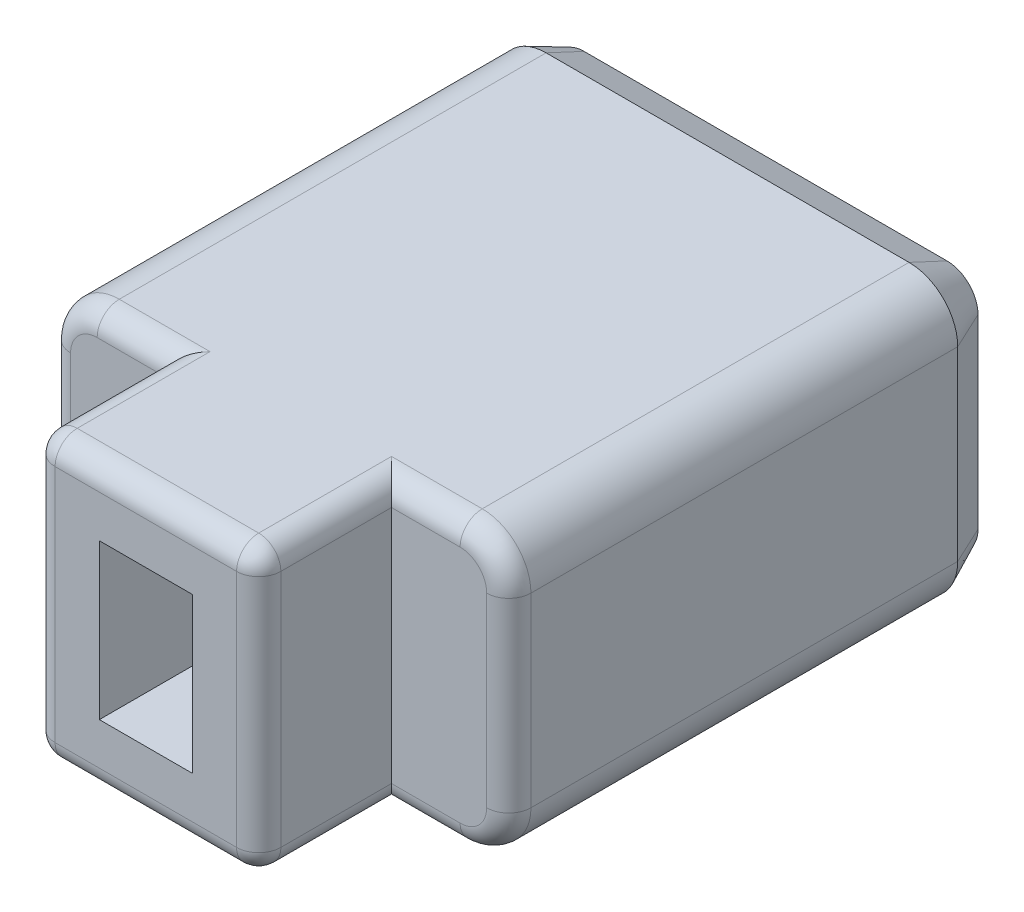
SolidWorks part; units mm, degrees
ref_plane "Plan de face" through (0, 0, 0) normal (0, 0, 1) x (1, 0, 0)
ref_plane "Plan de dessus" through (0, 0, 0) normal (0, 1, 0) x (1, 0, 0)
ref_plane "Plan de droite" through (0, 0, 0) normal (1, 0, 0) x (0, 0, -1)
sketch "Esquisse2" plane through (0, 0, 0) normal (0, 0, 1) x (1, 0, 0)
  line L1 (1.1, 0) -> (9.3, 0)
  line L2 (0, 1.1) -> (0, 5.3)
  line L3 (1.1, 6.4) -> (9.3, 6.4)
  line L4 (10.4, 1.1) -> (10.4, 5.3)
  arc A0 (9.3, 6.4) -> (10.4, 5.3) centre (9.3, 5.3) cw
  arc A1 (9.3, 0) -> (10.4, 1.1) centre (9.3, 1.1) ccw
  arc A2 (1.1, 0) -> (0, 1.1) centre (1.1, 1.1) cw
  arc A3 (0, 5.3) -> (1.1, 6.4) centre (1.1, 5.3) cw
  point P7 (10.4, 6.4)
  point P12 (0, 0)
  point P15 (0, 6.4)
  dimension "D3" = 1.1
  dimension "D1" = 10.4
  dimension "D2" = 6.4
extrude "Boss.-Extru.1" add sketch "Esquisse2" along normal blind 14
sketch "Esquisse3" plane through (0, 0, 14) normal (0, 0, 1) x (1, 0, 0)
  line L0 (0, 5.3) -> (0, 1.1) construction
  line L1 (4.15, 4.95) -> (6.25, 4.95)
  line L2 (4.15, 4.95) -> (4.15, 1.45)
  line L3 (4.15, 1.45) -> (6.25, 1.45)
  line L4 (6.25, 4.95) -> (6.25, 1.45)
  line L5 (10.4, 1.1) -> (10.4, 5.3) construction
  line L6 (9.3, 6.4) -> (1.1, 6.4) construction
  line L7 (1.1, 0) -> (9.3, 0) construction
  dimension "D1" = 2.1
  dimension "D2" = 3.5
  dimension "D3" = 4.15
  dimension "D4" = 4.15
  dimension "D5" = 1.45
  dimension "D6" = 1.45
extrude "Enlèv. mat.-Extru.1" cut sketch "Esquisse3" against normal blind 3
sketch "Esquisse4" plane through (0, 0, 14) normal (0, 0, 1) x (1, 0, 0)
  line L0 (2.65, 6.4) -> (2.65, 0)
  line L1 (9.3, 6.4) -> (1.1, 6.4) construction
  line L2 (1.1, 0) -> (9.3, 0) construction
  line L3 (2.65, 0) -> (7.75, 0)
  line L4 (7.75, 0) -> (7.75, 6.4)
  line L5 (7.75, 6.4) -> (2.65, 6.4)
  line L6 (4.15, 4.95) -> (4.15, 1.45) construction
  line L7 (6.25, 1.45) -> (6.25, 4.95) construction
  dimension "D1" = 1.5
  dimension "D2" = 1.5
extrude "Enlèv. mat.-Extru.2" cut sketch "Esquisse4" against normal blind 3 flip side to cut
fillet "Congé1" radius 0.5 18 edges at (8.525, 0, 11) (10.0778, 0.3222, 11) (10.4, 3.2, 11) (10.0778, 6.0778, 11) (1.875, 6.4, 11) (0.3222, 6.0778, 11) (1.875, 0, 11) (0.3222, 0.3222, 11) (7.75, 6.4, 12.5) (2.65, 6.4, 12.5) (7.75, 0, 12.5) (2.65, 0, 12.5) (2.65, 3.2, 14) (5.2, 6.4, 14) (7.75, 3.2, 14) (5.2, 0, 14) (8.525, 6.4, 11) (0, 3.2, 11)
chamfer "Chanfrein1" distance 0.4 angle 65 8 edges at (5.2, 0, 0) (10.0778, 0.3222, 0) (0.3222, 0.3222, 0) (10.4, 3.2, 0) (0, 3.2, 0) (10.0778, 6.0778, 0) (0.3222, 6.0778, 0) (5.2, 6.4, 0) first distance on face at (5.2, 3.2, 0)
sketch "Esquisse5" plane through (0, 0, 0) normal (0, 0, -1) x (-1, 0, 0)
  line L0 (-0.4, 5.3) -> (-10, 5.3) construction
  arc A0 (-9.3, 6) -> (-10, 5.3) centre (-9.3, 5.3) ccw construction
  text T0 "IDT" font "Century Gothic" height 4.1
extrude "Enlèv. mat.-Extru.3" cut sketch "Esquisse5" against normal blind 0.3
extrude "Boss.-Extru.2" add sketch "Esquisse5<2>" along normal blind 0.3 separate body
sketch "Esquisse5<2>" plane through (0, 0, 0) normal (0, 0, -1) x (-1, 0, 0) same geometry as "Esquisse5"
